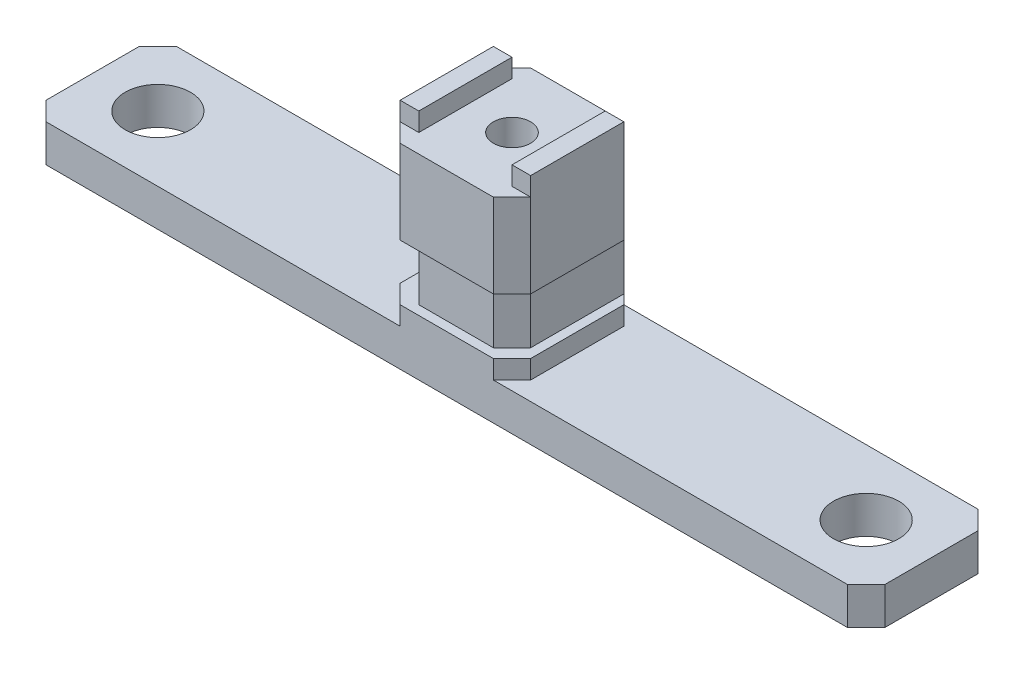
SolidWorks part; units mm, degrees
material "Plain Carbon Steel"
ref_plane "Front Plane" through (0, 0, 0) normal (0, 0, 1) x (1, 0, 0)
ref_plane "Top Plane" through (0, 0, 0) normal (0, 1, 0) x (1, 0, 0)
ref_plane "Right Plane" through (0, 0, 0) normal (1, 0, 0) x (0, 0, -1)
sketch "Sketch1" plane through (0, 0, 0) normal (0, 1, 0) x (1, 0, 0)
  line L1 (-45, -7) -> (45, -7)
  line L2 (-45, -7) -> (-45, 7)
  line L3 (-45, 7) -> (45, 7)
  line L4 (45, -7) -> (45, 7)
  line L5 (-45, -7) -> (45, 7) construction
  line L6 (-45, 7) -> (45, -7) construction
  circle A0 centre (-38, 0) radius 3.5
  circle A1 centre (38, 0) radius 3.5
  circle A2 centre (0, 0) radius 2
  point P0 (0, 0)
  point P12 (0, 0)
  point P13 (0, 0)
  dimension "D3" = 7
  dimension "D4" = 7
  dimension "D7" = 4
  dimension "D1" = 90
  dimension "D2" = 14
  dimension "D5" = 7
  dimension "D6" = 7
extrude "Boss-Extrude1" add sketch "Sketch1" along normal blind 4 contours L1 L4 L3 L2 A2 A1 A0 | A2 region at (-44.0892, 0, 0) region at (0, 0, 0)
sketch "Sketch2" plane through (0, 4, 0) normal (0, 1, 0) x (1, 0, 0)
  line L0 (-45, 7) -> (45, 7) construction
  line L1 (-7, -7) -> (7, -7)
  line L2 (-7, -7) -> (-7, 7)
  line L3 (-7, 7) -> (7, 7)
  line L4 (7, -7) -> (7, 7)
  line L5 (-7, -7) -> (7, 7) construction
  line L6 (-7, 7) -> (7, -7) construction
  point P0 (0, 0)
  dimension "D1" = 14
extrude "Boss-Extrude2" add sketch "Sketch2" along normal blind 2
sketch "Sketch3" plane through (0, 6, 0) normal (0, 1, 0) x (1, 0, 0)
  line L1 (-6, 6) -> (6, 6)
  line L2 (-6, 6) -> (-6, -6)
  line L3 (-6, -6) -> (6, -6)
  line L4 (6, 6) -> (6, -6)
  line L5 (-6, 6) -> (6, -6) construction
  line L6 (-6, -6) -> (6, 6) construction
  point P0 (0, 0)
  dimension "D1" = 12
extrude "Boss-Extrude3" add sketch "Sketch3" along normal blind 6
sketch "Sketch4" plane through (0, 12, 0) normal (0, 1, 0) x (1, 0, 0)
  line L0 (7, 7) -> (45, 7) construction
  line L1 (-7, -7) -> (7, -7)
  line L2 (-7, -7) -> (-7, 7)
  line L3 (-7, 7) -> (7, 7)
  line L4 (7, -7) -> (7, 7)
  line L5 (-7, -7) -> (7, 7) construction
  line L6 (-7, 7) -> (7, -7) construction
  line L7 (7, -7) -> (7, 7) construction
  point P0 (0, 0)
  dimension "D1" = 14
extrude "Boss-Extrude4" add sketch "Sketch4" along normal blind 9
sketch "Sketch5" plane through (0, 21, 0) normal (0, 1, 0) x (1, 0, 0)
  line L0 (-7, 7) -> (-7, -7) construction
  line L1 (-7, 5) -> (-5, 5)
  line L2 (-7, 5) -> (-7, -5)
  line L3 (-7, -5) -> (-5, -5)
  line L4 (-5, 5) -> (-5, -5)
  line L5 (7, -7) -> (7, 7) construction
  line L6 (5, 5) -> (7, 5)
  line L7 (5, 5) -> (5, -5)
  line L8 (5, -5) -> (7, -5)
  line L9 (7, 5) -> (7, -5)
  line L10 (-7, 0) -> (7, 0) construction
  dimension "D1" = 10
  dimension "D2" = 2
  dimension "D3" = 2
extrude "Boss-Extrude5" add sketch "Sketch5" along normal blind 2
sketch "Sketch6" plane through (0, 21, 0) normal (0, 1, 0) x (1, 0, 0)
  circle A0 centre (0, 0) radius 2
  dimension "D1" = 4
extrude "Cut-Extrude1" cut sketch "Sketch6" against normal up to surface (9 mm away) up to face at (0, 12, 0)
sketch "Sketch8" plane through (0, 12, 0) normal (0, 1, 0) x (1, 0, 0)
  circle A0 centre (0, 0) radius 4
  circle M2 centre (0, 0) radius 2
  dimension "D1" = 8
extrude "Cut-Extrude2" cut sketch "Sketch8" against normal through all contours A0 M2 | M2 region at (-3.8869, 12, 0) region at (0, 12, 0)
chamfer "Chamfer1" distance 2 angle 45 15 edges at (7, 5, 7) (6, 9, 6) (7, 16.5, 7) (7, 16.5, -7) (7, 5, -7) (-7, 5, 7) (-7, 5, -7) (-6, 9, -6) (-6, 9, 6) (-7, 16.5, 7) (45, 2, 7) (-45, 2, 7) (-45, 2, -7) (45, 2, -7) (-7, 16.5, -7)
chamfer "Chamfer2" distance 2 angle 45 1 edges at (0, 12, -2)
